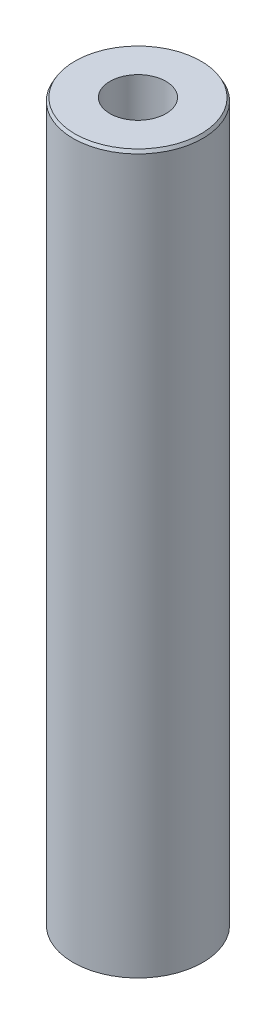
SolidWorks part; units mm, degrees
ref_plane "Front Plane" through (0, 0, 0) normal (0, 0, 1) x (1, 0, 0)
ref_plane "Top Plane" through (0, 0, 0) normal (0, 1, 0) x (1, 0, 0)
ref_plane "Right Plane" through (0, 0, 0) normal (1, 0, 0) x (0, 0, -1)
sketch "Sketch1" plane through (0, 0, 0) normal (0, 1, 0) x (1, 0, 0)
  circle A0 centre (0, 0) radius 50
  dimension "SHAFT_OD" = 100
extrude "Boss-Extrude1" add sketch "Sketch1" along normal blind 554.2149
sketch "Sketch2" plane through (0, 0, 0) normal (0, 1, 0) x (1, 0, 0)
  circle A0 centre (0, 0) radius 21.6041
  dimension "BORE_D" = 43.2081
extrude "Cut-Extrude1" cut sketch "Sketch2" along normal through all
chamfer "Chamfer1" distance 2.3871 angle 30 2 edges at (0, 554.2149, 50) (0, 0, 50) first distance on face at (0, 554.2149, 50) first distance on face at (0, 0, 21.6041)
